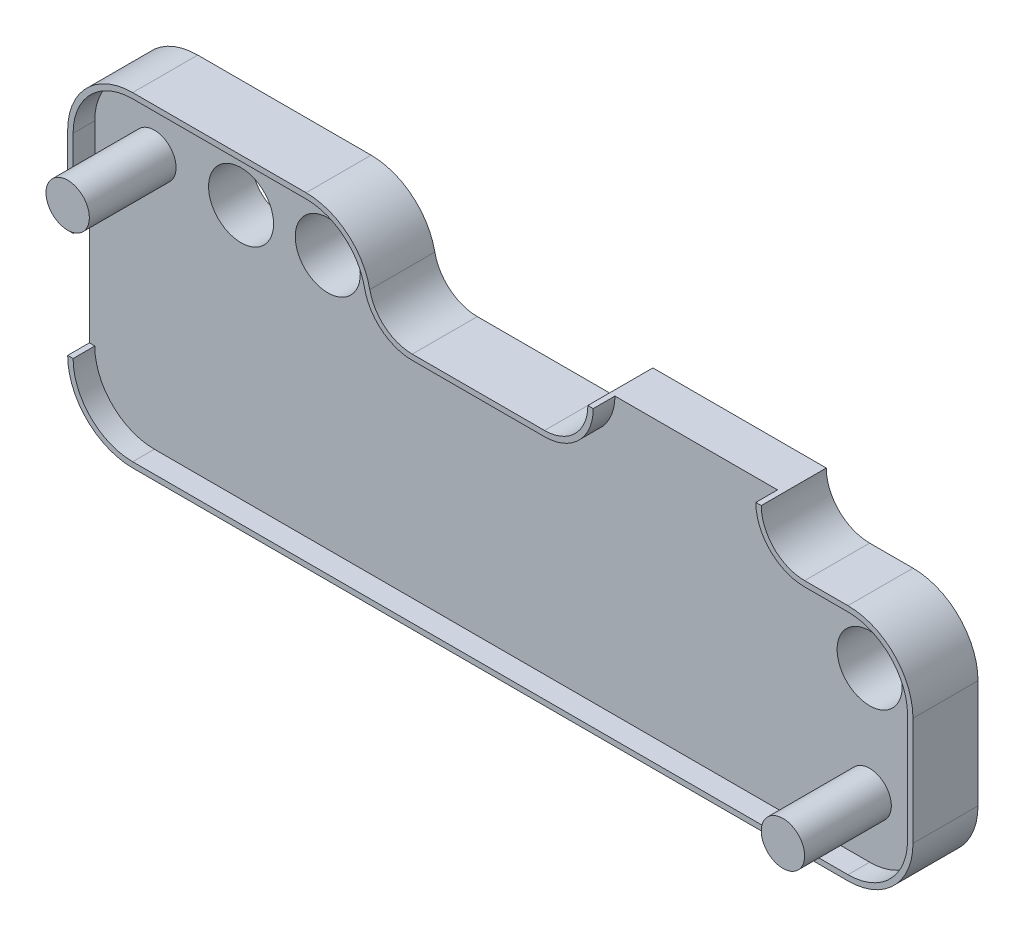
SolidWorks part; units mm, degrees
ref_plane "Front Plane" through (0, 0, 0) normal (0, 0, 1) x (1, 0, 0)
ref_plane "Top Plane" through (0, 0, 0) normal (0, 1, 0) x (1, 0, 0)
ref_plane "Right Plane" through (0, 0, 0) normal (1, 0, 0) x (0, 0, -1)
sketch "Sketch1" plane through (0, 0, 0) normal (0, 0, 1) x (1, 0, 0)
  line L0 (0, 0) -> (0, 15)
  line L1 (0, 15) -> (14, 15)
  line L2 (14, 15) -> (14, 11)
  line L3 (14, 11) -> (24, 11)
  line L4 (24, 11) -> (24, 13)
  line L5 (24, 13) -> (32, 13)
  line L6 (32, 13) -> (32, 11)
  line L7 (32, 11) -> (39, 11)
  line L8 (39, 11) -> (39, 0)
  line L9 (39, 0) -> (0, 0)
  point P11 (0, 0)
  dimension "D1" = 39
  dimension "D2" = 15
  dimension "D3" = 10
  dimension "D4" = 14
  dimension "D5" = 7
  dimension "D6" = 2
  dimension "D7" = 11
extrude "Boss-Extrude1" add sketch "Sketch1" along normal blind 2
fillet "Fillet1" radius 3 5 edges at (0, 0, 1) (39, 0, 1) (39, 11, 1) (0, 15, 1) (14, 15, 1)
fillet "Fillet2" radius 2 3 edges at (32, 11, 1) (24, 11, 1) (14, 11, 1)
sketch "Sketch3" plane through (0, 0, 2) normal (0, 0, 1) x (1, 0, 0)
  line L0 (0, 12) -> (0, 3) construction
  line L1 (3, 0) -> (36, 0) construction
  line L2 (39, 3) -> (39, 8) construction
  line L3 (36, 11) -> (34, 11) construction
  line L4 (0.25, 8) -> (0, 8)
  line L5 (22, 11) -> (15.899, 11) construction
  line L6 (11, 15) -> (3, 15) construction
  line L7 (0, 12) -> (0, 8)
  line L8 (3, 0) -> (36, 0)
  line L9 (39, 3) -> (39, 8)
  line L10 (36, 11) -> (34, 11)
  line L12 (22, 11) -> (15.899, 11)
  line L13 (11, 15) -> (3, 15)
  line L14 (22, 10.75) -> (15.899, 10.75)
  line L15 (11, 14.75) -> (3, 14.75)
  line L16 (0.25, 12) -> (0.25, 8)
  line L17 (3, 0.25) -> (36, 0.25)
  line L18 (38.75, 3) -> (38.75, 8)
  line L19 (36, 10.75) -> (34, 10.75)
  line L20 (24, 13) -> (24.25, 13)
  line L21 (32, 13) -> (31.75, 13)
  line L22 (0.25, 3) -> (0, 3)
  line L23 (0, 12) -> (0, 3) construction
  line L24 (0.25, 12) -> (0.25, 3) construction
  arc A0 (3, 15) -> (0, 12) centre (3, 12) ccw construction
  arc A1 (0, 3) -> (3, 0) centre (3, 3) ccw construction
  arc A2 (36, 0) -> (39, 3) centre (36, 3) ccw construction
  arc A3 (39, 8) -> (36, 11) centre (36, 8) ccw construction
  arc A4 (32, 13) -> (34, 11) centre (34, 13) ccw construction
  arc A5 (22, 11) -> (24, 13) centre (22, 13) ccw construction
  arc A6 (13.9394, 12.6) -> (15.899, 11) centre (15.899, 13) ccw construction
  arc A7 (13.9394, 12.6) -> (11, 15) centre (11, 12) ccw construction
  arc A8 (3, 15) -> (0, 12) centre (3, 12) ccw
  arc A9 (0, 3) -> (3, 0) centre (3, 3) ccw
  arc A10 (36, 0) -> (39, 3) centre (36, 3) ccw
  arc A11 (39, 8) -> (36, 11) centre (36, 8) ccw
  arc A12 (32, 13) -> (34, 11) centre (34, 13) ccw
  arc A13 (22, 11) -> (24, 13) centre (22, 13) ccw
  arc A14 (13.9394, 12.6) -> (15.899, 11) centre (15.899, 13) ccw
  arc A15 (13.9394, 12.6) -> (11, 15) centre (11, 12) ccw
  arc A16 (22, 10.75) -> (24.25, 13) centre (22, 13) ccw
  arc A17 (13.6944, 12.55) -> (15.899, 10.75) centre (15.899, 13) ccw
  arc A18 (13.6944, 12.55) -> (11, 14.75) centre (11, 12) ccw
  arc A19 (3, 14.75) -> (0.25, 12) centre (3, 12) ccw
  arc A20 (0.25, 3) -> (3, 0.25) centre (3, 3) ccw
  arc A21 (36, 0.25) -> (38.75, 3) centre (36, 3) ccw
  arc A22 (38.75, 8) -> (36, 10.75) centre (36, 8) ccw
  arc A23 (31.75, 13) -> (34, 10.75) centre (34, 13) ccw
  circle A24 centre (3, 12) radius 1
  circle A27 centre (11, 12) radius 1.5
  circle A28 centre (7, 12) radius 1.5
  circle A29 centre (36, 8) radius 1.5
  circle A30 centre (36, 3) radius 1
  point P54 (0, 0)
  dimension "D3" = 4
  dimension "D4" = 2
  dimension "D5" = 3
  dimension "D6" = 3
  dimension "D7" = 3
  dimension "D8" = 2
  dimension "D2" = 5
  dimension "D1" = 0.25
extrude "Cut-Extrude1" cut sketch "Sketch3" along direction (0, 0, -1) on the side against the normal up to surface (2 mm away) contours A28 | A27 | A29 | A28 | A27 region at (11, 12, 2) region at (7, 12, 2) region at (36, 8, 2) up to face at (20.5987, 9.1964, 0)
extrude "Boss-Extrude2" add sketch "Sketch3<4>" along normal blind 1 contours L24 A23 L19 A22 L18 A21 L17 A20 L22 L16 L20 L21 L23 | L13 A8 L7 L4 L16 A19 L15 A18 A17 L14 A16 L20 A13 L12 A14 A15 region at (1.0264, 1.0264, 2)
sketch "Sketch3<4>" plane through (0, 0, 2) normal (0, 0, 1) x (1, 0, 0) same geometry as "Sketch3"
extrude "Boss-Extrude3" add sketch "Sketch3<5>" along normal blind 4 contours A24 | A30 region at (3, 12, 2) region at (36, 3, 2)
sketch "Sketch3<5>" plane through (0, 0, 2) normal (0, 0, 1) x (1, 0, 0) same geometry as "Sketch3"
